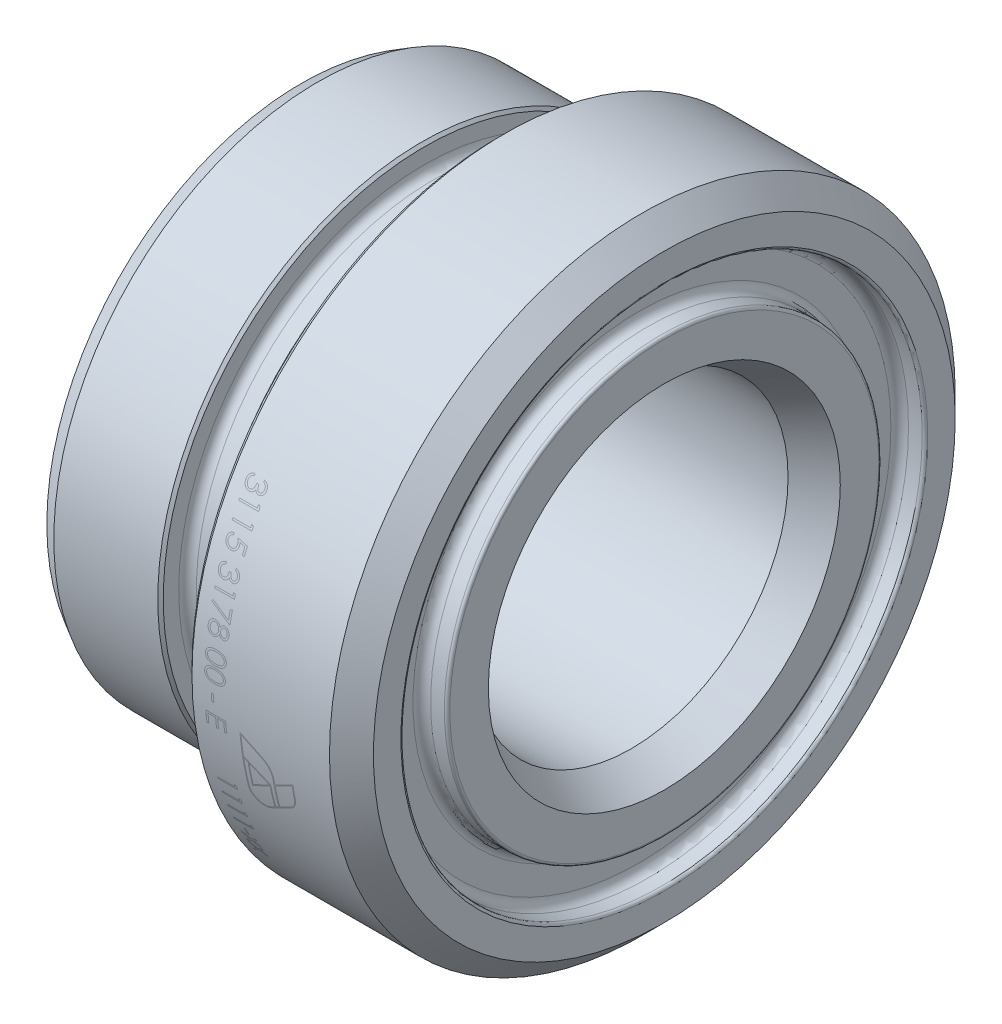
SolidWorks part; units mm, degrees
material "17CrNiMo6"
ref_plane "Front Plane" through (0, 0, 0) normal (0, 0, 1) x (1, 0, 0)
ref_plane "Top Plane" through (0, 0, 0) normal (0, 1, 0) x (1, 0, 0)
ref_plane "Right Plane" through (0, 0, 0) normal (1, 0, 0) x (0, 0, -1)
sketch "Sketch1" plane through (0, 0, 0) normal (0, 0, 1) x (1, 0, 0)
  line L0 (0, 16) -> (0, 19.75)
  line L1 (0, 19.75) -> (-1.5, 19.75)
  line L2 (-2.3, 20.55) -> (-2.3, 22.9)
  line L3 (-1.5, 23.7) -> (0, 23.7)
  line L4 (0, 23.7) -> (0, 26.445)
  line L5 (0, 26.445) -> (-2, 28.445)
  line L6 (-2, 28.445) -> (-15, 28.445)
  line L7 (-15, 28.445) -> (-15, 24.461)
  line L8 (-16.9, 24.01) -> (-18, 24.01)
  line L9 (-31.5, 24.01) -> (-33, 23.144)
  line L10 (-33, 23.144) -> (-33, 20.025)
  line L11 (-33, 20.025) -> (-26.8, 20.025)
  line L12 (-26, 19.225) -> (-26, 15.275)
  line L13 (-24.5, 14.25) -> (-3, 14.25)
  line L14 (-3, 14.25) -> (0, 16)
  line L15 (0, 0) -> (-33, 0) construction
  line L16 (-21.8, 24.01) -> (-21.8, 22.35)
  line L17 (-21, 21.55) -> (-18.8, 21.55)
  line L18 (-18, 22.35) -> (-18, 24.01)
  line L19 (-21.8, 24.01) -> (-31.5, 24.01)
  line L20 (-26, 15.275) -> (-24.5, 15.275)
  line L21 (-24.5, 15.275) -> (-24.5, 14.25)
  line L22 (-16.9, 24.01) -> (-16.0736, 23.7092)
  arc A0 (-16.0736, 23.7092) -> (-15, 24.461) centre (-15.8, 24.461) ccw
  arc A1 (-26.8, 20.025) -> (-26, 19.225) centre (-26.8, 19.225) cw
  arc A2 (-2.3, 22.9) -> (-1.5, 23.7) centre (-1.5, 22.9) cw
  arc A3 (-1.5, 19.75) -> (-2.3, 20.55) centre (-1.5, 20.55) cw
  arc A4 (-18.8, 21.55) -> (-18, 22.35) centre (-18.8, 22.35) ccw
  arc A5 (-21.8, 22.35) -> (-21, 21.55) centre (-21, 22.35) ccw
  dimension "D22" = 0.8
  dimension "D25" = 0.8
  dimension "D1" = 33
  dimension "D2" = 15
  dimension "D3" = 28.5
  dimension "D4" = 40.05
  dimension "D5" = 56.89
  dimension "D6" = 48.02
  dimension "D7" = 1.5
  dimension "D8" = 30
  dimension "D9" = 7
  dimension "D10" = 32
  dimension "D11" = 3
  dimension "D12" = 39.5
  dimension "D13" = 47.4
  dimension "D14" = 2.3
  dimension "D15" = 2
  dimension "D16" = 45
  dimension "D17" = 15
  dimension "D18" = 3.8
  dimension "D19" = 1.5
  dimension "D20" = 30.55
  dimension "D21" = 43.1
  dimension "D23" = 20
  dimension "D24" = 1.9
revolve "Revolve1" add sketch "Sketch1" angle 360 about L15
cosmetic thread "Cosmetic Thread1" parameters "D1"=14, "D2"=30
chamfer "Chamfer1" distance 0.5 angle 45 1 edges at (-15, 0, -28.445)
fillet "Fillet1" radius 0.25 1 edges at (-24.5, 0, -14.25)
fillet "Fillet2" radius 0.25 2 edges at (0, 0, -19.75) (0, 0, -23.7)
chamfer "Chamfer2" distance 0.25 angle 45 3 edges at (-18, 0, -24.01) (-21.8, 0, -24.01) (-33, 0, -20.025)
sketch "Sketch2" plane through (0, 0, 0) normal (0, 0, 1) x (1, 0, 0)
  line L0 (-13.3238, 20.3889) -> (-13.3238, -21.0896) construction
  text T0 "3115 3178 00 - E      1111-xx" font "Century Gothic" height 1.8
  line B0 (-10.2378, -7.0347) -> (-10.2378, -4.42)
  line B1 (-9.7048, -6.6474) -> (-9.7048, -4.7231)
  line B2 (-10.1578, -4.4655) -> (-9.7848, -4.6776)
  line B3 (-7.4825, -5.4264) -> (-7.4825, -4.9703)
  line B4 (-5.6713, -4.42) -> (-7.4825, -5.4264)
  line B5 (-9.7048, -6.6474) -> (-7.987, -5.6999)
  line B6 (-7.987, -7.8034) -> (-8.4001, -8.0424)
  line B7 (-5.6713, -5.7032) -> (-5.6713, -4.42)
  line B8 (-7.4825, -7.5282) -> (-7.987, -7.8034)
  line B9 (-7.4825, -7.5282) -> (-6.3172, -6.8372)
  line B10 (-10.2378, -4.42) -> (-10.2378, -2.422)
  line B11 (-8.2625, -3.5453) -> (-10.2378, -2.422)
  line B12 (-7.9068, -7.6868) -> (-7.5625, -7.4827)
  line B13 (-5.7513, -5.7032) -> (-5.7513, -4.5559)
  line B14 (-5.7513, -4.5559) -> (-7.4825, -5.5179)
  line B15 (-7.5625, -4.9703) -> (-7.5625, -7.4827)
  line B16 (-8.3039, -3.6138) -> (-10.1578, -2.5595)
  line B17 (-10.1578, -4.3734) -> (-10.1578, -2.5595)
  line B18 (-7.9068, -5.6535) -> (-7.9068, -7.6868)
  line B19 (-10.1578, -4.3734) -> (-7.9068, -5.6535)
  line B20 (-7.987, -7.711) -> (-8.4417, -7.974)
  line B21 (-10.1578, -7.0347) -> (-10.1578, -4.4655)
  line B22 (-7.4825, -5.5179) -> (-7.4825, -7.4352)
  line B23 (-7.4825, -7.4352) -> (-6.358, -6.7684)
  line B24 (-9.7848, -6.7829) -> (-9.7848, -4.6776)
  line B25 (-9.7848, -6.7829) -> (-7.987, -5.7912)
  line B26 (-7.987, -5.7912) -> (-7.987, -7.711)
  line B27 (-9.7048, -4.7231) -> (-7.987, -5.6999)
  arc B28 (-6.3172, -6.8372) -> (-5.6713, -5.7032) centre (-6.9897, -5.7032) ccw
  arc B29 (-10.2378, -7.0347) -> (-8.4001, -8.0424) centre (-9.0427, -7.0347) ccw
  arc B30 (-7.4825, -4.9703) -> (-8.2625, -3.5453) centre (-9.1742, -4.9703) ccw
  arc B31 (-6.358, -6.7684) -> (-5.7513, -5.7032) centre (-6.9897, -5.7032) ccw
  arc B32 (-7.5625, -4.9703) -> (-8.3039, -3.6138) centre (-9.1742, -4.9703) ccw
  arc B33 (-10.1578, -7.0347) -> (-8.4417, -7.974) centre (-9.0427, -7.0347) ccw
  dimension "D1" = 13.3238
sketch_block_instance "SKETCH LOGO-1"
sketch_block "SKETCH LOGO" parameters "D1"=29.059, "D2"=11.4163, "D3"=29.624, "D4"=6.8884
sketch "Sketch3" plane through (0, 0, 0) normal (0, 0, 1) x (1, 0, 0)
  line L0 (-8.8, 28.445) -> (-8.8, 26.9)
  line L1 (-2, 28.445) -> (-15, 28.445) construction
  line L2 (-8, 26.1) -> (-5.8, 26.1)
  line L3 (-5, 26.9) -> (-5, 28.445)
  line L4 (-8.8, 28.445) -> (-5, 28.445)
  line L5 (0, 0) -> (-38.5704, 0) construction
  line L6 (0, 23.7) -> (0, 26.445) construction
  arc A0 (-5.8, 26.1) -> (-5, 26.9) centre (-5.8, 26.9) ccw
  arc A1 (-8.8, 26.9) -> (-8, 26.1) centre (-8, 26.9) ccw
  dimension "D4" = 0.8
  dimension "D1" = 3.8
  dimension "D2" = 52.2
  dimension "D3" = 5
revolve "Cut-Revolve1" [suppressed] cut sketch "Sketch3" angle 360 about L5
chamfer "Chamfer3" [suppressed] distance 0.25 angle 45
wrap "Wrap1" sketch "Sketch2" wrap type scribe source sketch "Sketch2" face at (-14.5, 0, 28.445)
